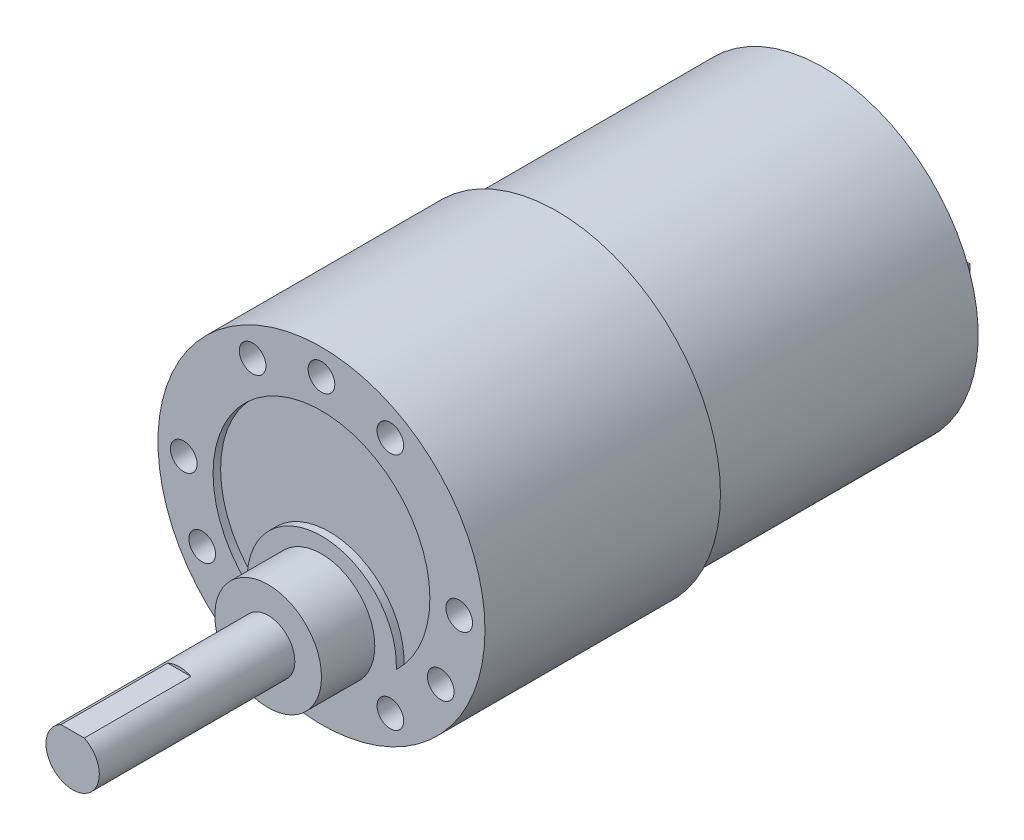
SolidWorks part; units mm, degrees
ref_plane "Alzado" through (0, 0, 0) normal (0, 0, 1) x (1, 0, 0)
ref_plane "Planta" through (0, 0, 0) normal (0, 1, 0) x (1, 0, 0)
ref_plane "Vista lateral" through (0, 0, 0) normal (1, 0, 0) x (0, 0, -1)
sketch "Croquis1" plane through (0, 0, 0) normal (0, 0, 1) x (1, 0, 0)
  circle A0 centre (0, 0) radius 18.4
  dimension "D1" = 36.8
extrude "Saliente-Extruir1" add sketch "Croquis1" along normal blind 26.5
sketch "Croquis2" plane through (0, 0, 26.5) normal (0, 0, 1) x (1, 0, 0)
  line L0 (0, 30.4942) -> (0, -33.5704) construction
  arc A0 (8.419, -8.8295) -> (-8.3557, -8.8894) centre (0, 0) ccw
  circle A1 centre (0, 0) radius 18.4
  circle A2 centre (0, 0) radius 18.4
  circle A4 centre (0, 0) radius 12.2 construction
  arc A6 (-8.3557, -8.8894) -> (8.419, -8.8295) centre (0.03, -8.3999) cw
  point P14 (0, 0)
  point P15 (0, 0)
  dimension "D5" = 8.4
  dimension "D6" = 16.7747
  dimension "D1" = 0
  dimension "D2" = 6.2
extrude "Cortar-Extruir2" cut sketch "Croquis2" against normal blind 0.85 contours A0 L0 | L0 A0 | A0 A6 region at (-0.0115, 3.2069, 26.5)
sketch "Croquis3" plane through (0, 0, 26.5) normal (0, 0, 1) x (1, 0, 0)
  line L0 (0, 31.1583) -> (0, -27.634) construction
  line L1 (0, 0) -> (0, 15.5) construction
  line L2 (0, 0) -> (13.4234, -7.75) construction
  circle A0 centre (0, 15.5) radius 1.5
  circle A1 centre (13.4234, -7.75) radius 1.5
  circle A2 centre (-13.4234, -7.75) radius 1.5
  dimension "D1" = 3
  dimension "D2" = 15.5
  dimension "D4" = 120
  dimension "D5" = 15.5
  dimension "D6" = 120
  dimension "D3" = 3
extrude "Cortar-Extruir3" cut sketch "Croquis3" against normal blind 25
sketch "Croquis9" plane through (0, 0, 26.5) normal (0, 0, 1) x (1, 0, 0)
  line L0 (0, 24.3626) -> (0, -23.3935) construction
  line L1 (-26.4176, 0) -> (25.549, 0) construction
  line L2 (0, 0) -> (-15.5, 0) construction
  circle A0 centre (-15.5, 0) radius 1.5
  circle A1 centre (-7.75, 13.4234) radius 1.5
  circle A2 centre (7.75, 13.4234) radius 1.5
  circle A3 centre (15.5, 0) radius 1.5
  circle A4 centre (7.75, -13.4234) radius 1.5
  circle A5 centre (-7.75, -13.4234) radius 1.5
  dimension "D1" = 3
  dimension "D2" = 15.5
  dimension "D4" = 15.5
  dimension "D3" = 6
extrude "Cortar-Extruir4" cut sketch "Croquis9" against normal blind 5
sketch "Croquis22" plane through (0, 0, 26.5) normal (0, 0, 1) x (1, 0, 0)
  line L0 (13.4234, -7.75) -> (-13.4234, -7.75) construction
  circle A0 centre (0, -7.75) radius 6
  circle A1 centre (0, 0) radius 18.4
  circle A2 centre (0, 0) radius 18.4
  dimension "D2" = 12
  dimension "D1" = 0
extrude "Saliente-Extruir2" add sketch "Croquis22" along normal blind 6 contours A0
sketch "Croquis24" plane through (0, 0, 32.5) normal (0, 0, 1) x (1, 0, 0)
  circle A0 centre (0, -7.75) radius 3
  dimension "D1" = 6
extrude "Saliente-Extruir3" add sketch "Croquis24" along normal blind 22
sketch "Croquis25" plane through (0, 0, 54.5) normal (0, 0, 1) x (1, 0, 0)
  line L0 (4.0248, -7.75) -> (-5.0416, -7.75) construction
  line L1 (0, -3.7978) -> (0, -11.5749) construction
  line L2 (-1.3077, -5.05) -> (1.3077, -5.05)
  circle A0 centre (0, -7.75) radius 3 construction
  circle A1 centre (0, -7.75) radius 3
  point P10 (0, 0)
  point P11 (0, 0)
  circle M4 centre (0, -7.75) radius 3
  dimension "D1" = 2.7
extrude "Cortar-Extruir5" cut sketch "Croquis25" against normal blind 12 contours L2 M4 region at (0, -4.9295, 54.5)
sketch "Croquis26" plane through (0, 0, 0) normal (0, 0, -1) x (-1, 0, 0)
  circle A0 centre (0, 0) radius 17.4
  circle A1 centre (0, 0) radius 18.4
  circle A2 centre (0, 0) radius 18.4
  dimension "D1" = 0
  dimension "D2" = 1
extrude "Saliente-Extruir4" add sketch "Croquis26" along normal blind 30 contours A0
sketch "Croquis27" plane through (0, 0, -30) normal (0, 0, -1) x (-1, 0, 0)
  line L0 (-25.3398, 0) -> (26.5759, 0) construction
  line L1 (0, 15.9533) -> (0, -14.6399) construction
  line L2 (11.5, -1.5) -> (11, 1.5) construction
  line L3 (-11.5, -1.5) -> (-11, -1.5)
  line L4 (-11.5, -1.5) -> (-11.5, 1.5)
  line L5 (-11.5, 1.5) -> (-11, 1.5)
  line L6 (-11, -1.5) -> (-11, 1.5)
  line L7 (-11.5, -1.5) -> (-11, 1.5) construction
  line L8 (-11.5, 1.5) -> (-11, -1.5) construction
  line L9 (11.5, 1.5) -> (11, -1.5) construction
  line L10 (11.5, 1.5) -> (11, 1.5)
  line L11 (11, -1.5) -> (11, 1.5)
  line L12 (11.5, -1.5) -> (11, -1.5)
  line L13 (11.5, -1.5) -> (11.5, 1.5)
  circle A0 centre (0, 0) radius 3.9
  circle A1 centre (-11.25, 0) radius 2.25
  circle A2 centre (11.25, 0) radius 2.25
  dimension "D1" = 7.8
  dimension "D2" = 4.5
  dimension "D3" = 11.25
  dimension "D4" = 3
  dimension "D5" = 0.5
extrude "Saliente-Extruir5" add sketch "Croquis27" along normal blind 1.6
sketch "Croquis29" plane through (0, 0, -30) normal (0, 0, -1) x (-1, 0, 0)
  line L0 (-11, -1.5) -> (-11, 1.5) construction
  line L1 (-11, 1.5) -> (-11.5, 1.5) construction
  line L2 (-11.5, 1.5) -> (-11.5, -1.5) construction
  line L3 (-11.5, -1.5) -> (-11, -1.5) construction
  line L4 (11.5, -1.5) -> (11.5, 1.5) construction
  line L5 (11.5, 1.5) -> (11, 1.5) construction
  line L6 (11, 1.5) -> (11, -1.5) construction
  line L7 (11, -1.5) -> (11.5, -1.5) construction
  line L8 (-11, -1.5) -> (-11, 1.5)
  line L9 (-11, 1.5) -> (-11.5, 1.5)
  line L10 (-11.5, 1.5) -> (-11.5, -1.5)
  line L11 (-11.5, -1.5) -> (-11, -1.5)
  line L12 (11.5, -1.5) -> (11.5, 1.5)
  line L13 (11.5, 1.5) -> (11, 1.5)
  line L14 (11, 1.5) -> (11, -1.5)
  line L15 (11, -1.5) -> (11.5, -1.5)
extrude "Saliente-Extruir6" add sketch "Croquis29" along normal blind 5
